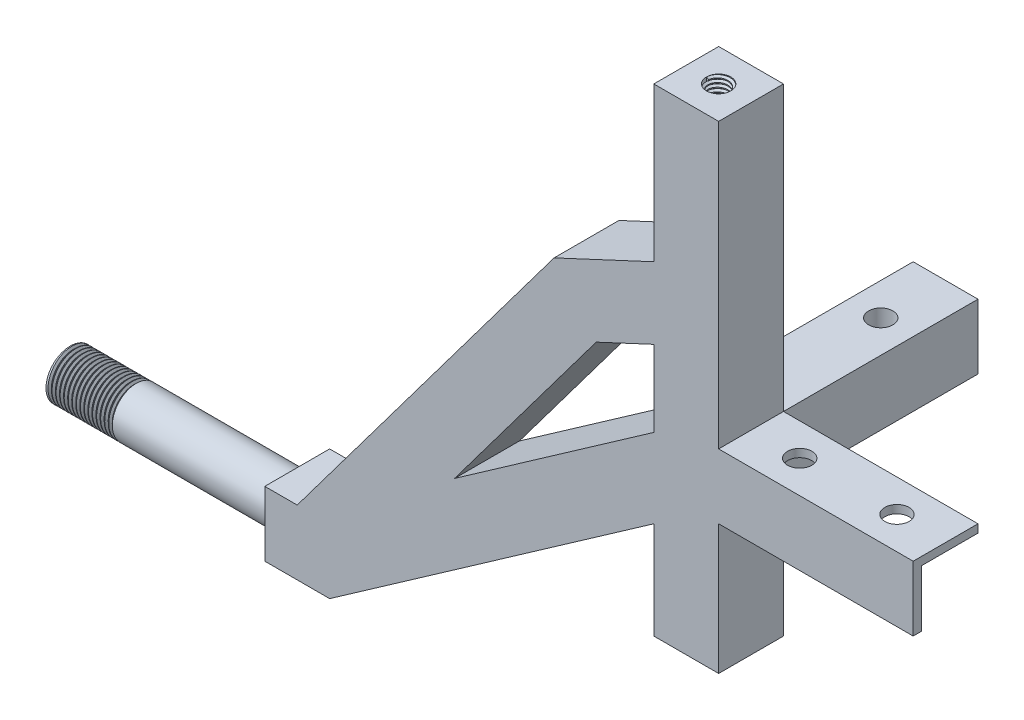
SolidWorks part; units mm, degrees
material "Plain Carbon Steel"
ref_plane "Front Plane" through (0, 0, 0) normal (0, 0, 1) x (1, 0, 0)
ref_plane "Top Plane" through (0, 0, 0) normal (0, 1, 0) x (1, 0, 0)
ref_plane "Right Plane" through (0, 0, 0) normal (1, 0, 0) x (0, 0, -1)
sketch "Sketch1" plane through (0, 0, 0) normal (0, 1, 0) x (1, 0, 0)
  line L1 (12.7, -12.7) -> (-12.7, -12.7)
  line L2 (12.7, -12.7) -> (12.7, 12.7)
  line L3 (12.7, 12.7) -> (-12.7, 12.7)
  line L4 (-12.7, -12.7) -> (-12.7, 12.7)
  line L5 (12.7, -12.7) -> (-12.7, 12.7) construction
  line L6 (12.7, 12.7) -> (-12.7, -12.7) construction
  line L7 (10.16, -10.16) -> (-10.16, -10.16)
  line L8 (10.16, -10.16) -> (10.16, 10.16)
  line L9 (10.16, 10.16) -> (-10.16, 10.16)
  line L10 (-10.16, -10.16) -> (-10.16, 10.16)
  line L11 (10.16, -10.16) -> (-10.16, 10.16) construction
  line L12 (10.16, 10.16) -> (-10.16, -10.16) construction
  point P0 (0, 0)
  point P5 (0, 0)
  dimension "D1" = 2.54
  dimension "1" = 25.4
extrude "Sq_Tb Extrude" add sketch "Sketch1" along normal blind 187.325
sketch "Sketch3" plane through (0, 187.325, 0) normal (0, 1, 0) x (1, 0, 0)
  line L1 (10.16, -10.16) -> (-10.16, -10.16)
  line L2 (10.16, -10.16) -> (10.16, 10.16)
  line L3 (10.16, 10.16) -> (-10.16, 10.16)
  line L4 (-10.16, -10.16) -> (-10.16, 10.16)
  line L5 (10.16, -10.16) -> (-10.16, 10.16) construction
  line L6 (10.16, 10.16) -> (-10.16, -10.16) construction
  circle A0 centre (0, 0) radius 4.7625
  point P0 (0, 0)
  dimension "D1" = 9.525
extrude "End Caps" add sketch "Sketch3" against normal blind 6.35
ref_plane "Mid-Plane" through (0, 93.6625, 0) normal (0, 1, 0) x (1, 0, 0)
mirror "End Cap Mirror" about plane through (0, 93.6625, 0) normal (0, 1, 0) of "End Caps"
thread "Top Thread" pitch 1.5875 method extrude profile "Thread Profile1" start angle 0, offset 0, length 0, pitch 1.5875, diameter 9.525
ref_plane "Plane2" through (-4.7625, 187.325, 0) normal (0, 0, 1) x (-1, 0, 0)
sketch "Thread Profile1" plane through (-4.7625, 187.325, 0) normal (0, 0, 1) x (-1, 0, 0)
  line L0 (0, 0) -> (0, 1.5875) construction
  line L11 (0, 0) -> (0, 1.3891)
  line L12 (0, 1.3891) -> (-0.8593, 0.893)
  line L13 (-0.8593, 0.893) -> (-0.8593, 0.4961)
  line L15 (-0.8593, 0.4961) -> (0, 0)
  line L17 (-0.8593, 0.6945) -> (0, 0.6945) construction
  point P2 (0, 0)
  dimension "Pitch" = 1.5875
  dimension "Profile_Angle" = 60
  dimension "Profile_Land" = 0.3969
  dimension "Profile_Height" = 0.8593
thread "Bottom Thread" pitch 1.5875 method extrude profile "Thread Profile2" start angle 0, offset 0, length 0, pitch 1.5875, diameter 9.525
ref_plane "Plane3" through (4.7625, 0, 0) normal (0, 0, 1) x (1, 0, 0)
sketch "Thread Profile2" plane through (4.7625, 0, 0) normal (0, 0, 1) x (1, 0, 0)
  line L0 (0, 0) -> (0, 1.5875) construction
  line L11 (0, 0) -> (0, 1.3891)
  line L12 (0, 1.3891) -> (-0.8593, 0.893)
  line L13 (-0.8593, 0.893) -> (-0.8593, 0.4961)
  line L15 (-0.8593, 0.4961) -> (0, 0)
  line L17 (-0.8593, 0.6945) -> (0, 0.6945) construction
  point P2 (0, 0)
  dimension "Pitch" = 1.5875
  dimension "Profile_Angle" = 60
  dimension "Profile_Land" = 0.3969
  dimension "Profile_Height" = 0.8593
sketch "Sketch9" plane through (0, 0, 0) normal (0, 0, 1) x (1, 0, 0)
  line L0 (-12.7, 126.996) -> (-51.7653, 108.7796)
  line L1 (-12.7, 187.325) -> (-12.7, 0) construction
  line L2 (-102.0827, 41.6898) -> (-81.7627, 26.4498) construction
  line L3 (-35.2635, 88.4487) -> (-12.7, 98.9702)
  line L4 (-12.7, 38.0909) -> (-139.7, -50.8)
  line L5 (-90.7525, 14.4633) -> (-12.7, 69.0945)
  line L6 (-12.7, 69.0945) -> (-12.7, 38.0909)
  line L8 (-51.7653, 108.7796) -> (-152.4, -25.4)
  line L9 (-12.7, 126.996) -> (-12.7, 98.9702)
  line L10 (-139.7, -50.8) -> (-35.2635, 88.4487)
  line L11 (-139.7, -50.8) -> (-165.1, -50.8)
  line L12 (-165.1, -50.8) -> (-165.1, -25.4)
  line L13 (-165.1, -25.4) -> (-152.4, -25.4)
  line L14 (-32.2327, 117.8878) -> (-21.4982, 94.8676) construction
  line L15 (-165.1, -38.1) -> (0, -38.1) construction
  line L16 (0, -38.1) -> (0, 0) construction
  line L18 (-12.7, 0) -> (12.7, 0) construction
  line L19 (-51.7262, 41.7789) -> (-37.1613, 20.9697) construction
  line L20 (-12.7, 69.0945) -> (32.9312, 3.9003) construction
  line L21 (-139.7, -50.8) -> (-114.9192, -86.2048) construction
  dimension "D3" = 172.7962
  dimension "D1" = 25.4
  dimension "D2" = 43.1038
  dimension "D4" = 65
  dimension "D5" = 12.7
  dimension "D6" = 152.4
  dimension "D7" = 115
  dimension "D8" = 25.4
  dimension "D9" = 50.8
  dimension "D10" = 55.011
  dimension "D11" = 60.329
  dimension "D12" = 38.0909
  dimension "D13" = 88.9052
extrude "Sq_Tb Angles" add sketch "Sketch9" along normal blind 12.7 and the other way blind 12.7 contours L13 L12 L11 L10 L3 L9 L0 L8 | L10 L4 L6 L5 region at (-89.8222, 35.9011, 0) region at (-64.9368, 15.7972, 0)
sketch "Sketch11" plane through (0, 0, 0) normal (0, 0, 1) x (1, 0, 0)
  line L0 (-165.1, -38.1) -> (-254, -38.1)
  line L1 (-165.1, -50.8) -> (-165.1, -25.4) construction
  line L2 (-254, -38.1) -> (-254, -28.575)
  line L3 (-254, -28.575) -> (-165.1, -28.575)
  line L6 (-165.1, -28.575) -> (-165.1, -38.1)
  dimension "D2" = 9.525
  dimension "D4" = 88.9
revolve "Wheel Rod" add sketch "Sketch11" angle 360 about L0
thread "Wheel Threads" pitch 1.5875 method cut profile "Thread Profile3" start angle 0, offset 0, length 25.4, pitch 1.5875, diameter 19.05
ref_plane "Plane4" through (-254, -38.1, -9.525) normal (0, -1, 0) x (0, 0, -1)
sketch "Thread Profile3" plane through (-254, -38.1, -9.525) normal (0, -1, 0) x (0, 0, -1)
  line L0 (0, 0) -> (0, 1.5875) construction
  line L11 (0, 0) -> (0, 1.3891)
  line L12 (0, 1.3891) -> (-0.8593, 0.893)
  line L13 (-0.8593, 0.893) -> (-0.8593, 0.4961)
  line L15 (-0.8593, 0.4961) -> (0, 0)
  line L17 (-0.8593, 0.6945) -> (0, 0.6945) construction
  point P2 (0, 0)
  dimension "Pitch" = 1.5875
  dimension "Profile_Angle" = 60
  dimension "Profile_Land" = 0.3969
  dimension "Profile_Height" = 0.8593
ref_plane "Tie-Rod Mount Plane" through (0, 34.925, 0) normal (0, 1, 0) x (1, 0, 0)
sketch "Sketch15" plane through (0, 34.925, 0) normal (0, 1, 0) x (1, 0, 0)
  line L0 (0, 12.7) -> (12.7, 25.4)
  line L1 (12.7, 12.7) -> (-12.7, 12.7) construction
  line L2 (12.7, 25.4) -> (76.2, 25.4)
  line L3 (0, -12.7) -> (12.7, -25.4)
  line L4 (-12.7, -12.7) -> (12.7, -12.7) construction
  line L5 (0, 12.7) -> (12.7, 12.7)
  line L6 (12.7, -12.7) -> (12.7, 12.7) construction
  line L7 (12.7, 12.7) -> (12.7, -12.7)
  line L8 (12.7, -12.7) -> (0, -12.7)
  line L9 (12.7, -25.4) -> (76.2, -25.4)
  line L10 (76.2, -25.4) -> (76.2, 25.4) construction
  line L11 (12.7, 25.4) -> (12.7, 12.7) construction
  line L12 (12.7, -12.7) -> (12.7, -25.4) construction
  line L13 (76.2, 25.4) -> (88.9, 12.7)
  line L14 (88.9, 12.7) -> (88.9, -12.7)
  line L15 (88.9, -12.7) -> (76.2, -25.4)
  line L16 (12.7, 0) -> (88.9, 0) construction
  dimension "D1" = 12.7
  dimension "D2" = 76.2
  dimension "D3" = 12.7
extrude "Tie-Rod Mount Plate" [suppressed] add sketch "Sketch15" along normal blind 6.35
sketch "Sketch16" [suppressed] plane through (0, 41.275, 0) normal (0, 1, 0) x (1, 0, 0)
  line L0 (12.7, 0) -> (63.5, 0) construction
  line L1 (12.7, -12.7) -> (12.7, 12.7) construction
  line L2 (63.5, 0) -> (63.5, 15.875) construction
  line L3 (12.7, 0) -> (76.2, 0) construction
  circle A0 centre (63.5, 15.875) radius 4.7625
  circle A1 centre (63.5, -15.875) radius 4.7625
  circle A2 centre (76.2, 0) radius 4.7625
  dimension "D1" = 50.8
  dimension "D3" = 9.525
  dimension "D2" = 15.875
  dimension "D4" = 63.5
extrude "Tie-Rod Mount Hole" [suppressed] cut sketch "Sketch16" against normal through all
ref_plane "Plane5" through (0, 50.8, 0) normal (0, -1, 0) x (-1, 0, 0)
sketch "Sketch17" plane through (0, 50.8, 0) normal (0, -1, 0) x (-1, 0, 0)
  line L0 (-12.7, -12.7) -> (-12.7, 12.7) construction
  line L1 (-12.7, 12.7) -> (12.7, 12.7)
  line L2 (-12.7, 12.7) -> (-12.7, 88.9)
  line L3 (-12.7, 88.9) -> (12.7, 88.9)
  line L4 (12.7, 12.7) -> (12.7, 88.9)
  line L5 (-12.7, 12.7) -> (12.7, 88.9) construction
  line L6 (-12.7, 88.9) -> (12.7, 12.7) construction
  line L7 (-12.7, 12.7) -> (12.7, 12.7) construction
  point P4 (0, 50.8)
  dimension "D1" = 25.4
  dimension "D2" = 76.2
extrude "Boss-Extrude1" add sketch "Sketch17" against normal blind 25.4
sketch "Sketch18" plane through (0, 76.2, 0) normal (0, 1, 0) x (1, 0, 0)
  line L0 (0, 0) -> (0, 63.5) construction
  circle A0 centre (0, 63.5) radius 4.7625
  dimension "D1" = 63.5
  dimension "D2" = 9.525
extrude "Cut-Extrude1" cut sketch "Sketch18" against normal through all
sketch "Sketch19" plane through (12.7, 0, 0) normal (1, 0, 0) x (0, 0, -1)
  line L0 (12.7, 76.2) -> (-12.7, 76.2)
  line L1 (-12.7, 187.325) -> (-12.7, 0) construction
  line L2 (-12.7, 76.2) -> (-12.7, 50.8)
  line L3 (-65.0506, 50.8) -> (65.0506, 50.8) construction
  line L4 (-12.7, 50.8) -> (-9.525, 50.8)
  line L5 (-9.525, 50.8) -> (-9.525, 73.025)
  line L6 (-9.525, 73.025) -> (12.7, 73.025)
  line L7 (12.7, 73.025) -> (12.7, 76.2)
  dimension "D1" = 3.175
extrude "Boss-Extrude2" add sketch "Sketch19" along normal blind 76.2
sketch "Sketch20" plane through (0, 76.2, 0) normal (0, 1, 0) x (1, 0, 0)
  line L0 (50.8, -12.7) -> (50.8, 0) construction
  line L2 (88.9, -12.7) -> (12.7, -12.7) construction
  line L3 (0, 0) -> (31.75, 0) construction
  line L4 (31.75, 0) -> (69.85, 0) construction
  circle A0 centre (69.85, 0) radius 4.7625
  circle A1 centre (31.75, 0) radius 4.7625
  point P8 (50.8, 0)
  dimension "D1" = 31.75
  dimension "D2" = 9.525
  dimension "D3" = 69.85
extrude "Cut-Extrude2" cut sketch "Sketch20" against normal through all
